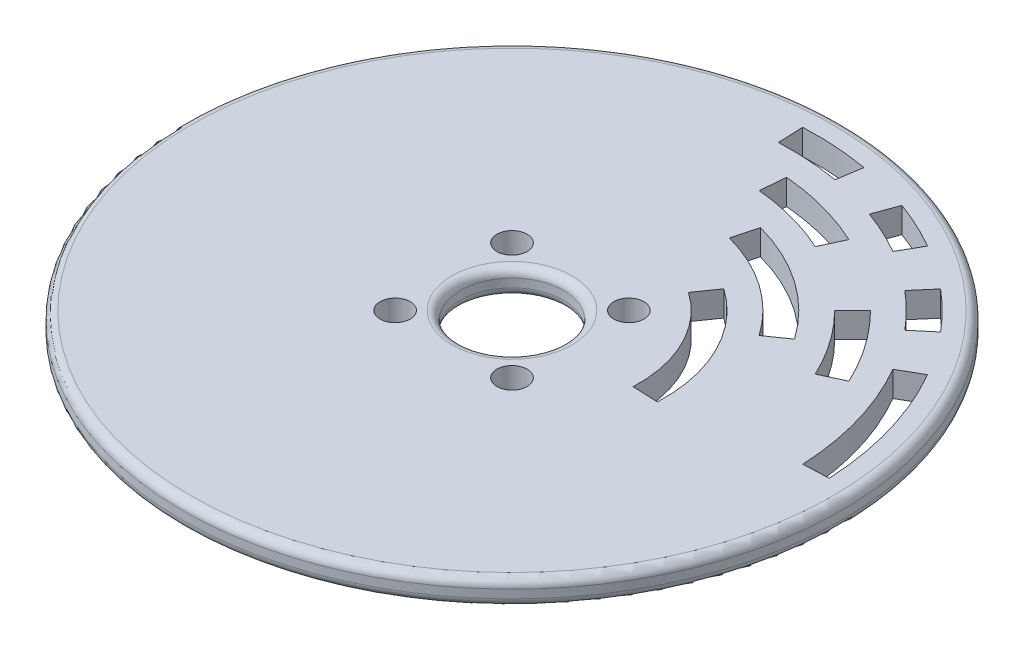
SolidWorks part; units mm, degrees
ref_plane "Front Plane" through (0, 0, 0) normal (0, 0, 1) x (1, 0, 0)
ref_plane "Top Plane" through (0, 0, 0) normal (0, 1, 0) x (1, 0, 0)
ref_plane "Right Plane" through (0, 0, 0) normal (1, 0, 0) x (0, 0, -1)
sketch "Sketch1" plane through (0, 0, 0) normal (0, 1, 0) x (1, 0, 0)
  line L0 (0, 0) -> (8.1776, 8.1776) construction
  circle A0 centre (0, 0) radius 6.096
  circle A1 centre (6.9148, 6.9148) radius 1.7859
  circle A2 centre (6.9148, -6.9148) radius 1.7859
  circle A3 centre (-6.9148, -6.9148) radius 1.7859
  circle A4 centre (-6.9148, 6.9148) radius 1.7859
  point P18 (0, 0)
  dimension "D2" = 3.5719
  dimension "D3" = 4
sketch "Sketch3" plane through (0, 0, 0) normal (0, 1, 0) x (1, 0, 0)
  line L1 (-1.4394, 32.9686) -> (-1.5703, 35.9657) construction
  line L8 (8.6036, 12.2873) -> (10.3244, 14.7447) construction
  line L15 (32.9686, 1.4394) -> (35.9657, 1.5703)
  line L17 (-1.5703, 35.9657) -> (-1.4394, 32.9686)
  line L18 (6.1868, 35.4644) -> (5.7304, 32.4987)
  line L19 (12.3127, 33.8289) -> (11.2867, 31.0099)
  line L20 (18, 31.1769) -> (16.5, 28.5788)
  line L23 (14.9857, -0.6543) -> (17.9829, -0.7851) construction
  line L24 (23.1635, 27.5582) -> (21.212, 25.2795)
  line L25 (27.5776, 23.1404) -> (25.2795, 21.212)
  line L26 (31.1769, 18) -> (28.5788, 16.5)
  line L28 (14.9857, -0.6543) -> (17.9829, -0.7851)
  line L29 (11.2867, 31.0099) -> (12.3127, 33.8289) construction
  line L30 (10.3244, 14.7447) -> (8.6036, 12.2873)
  line L32 (16.5, 28.5788) -> (18, 31.1769) construction
  line L34 (23.3345, 23.3345) -> (25.4558, 25.4558) construction
  line L35 (25.2795, 21.212) -> (27.5776, 23.1404) construction
  line L36 (28.5788, 16.5) -> (31.1769, 18) construction
  line L37 (32.9686, 1.4394) -> (35.9657, 1.5703) construction
  line L38 (2.6147, 29.8858) -> (2.3532, 26.8973)
  line L39 (12.6785, 27.1892) -> (11.4107, 24.4703)
  line L40 (21.2132, 21.2132) -> (19.0919, 19.0919)
  line L41 (27.1892, 12.6785) -> (24.4703, 11.4107)
  line L42 (24.4703, 11.4107) -> (27.1892, 12.6785) construction
  line L43 (2.3532, 26.8973) -> (2.6147, 29.8858) construction
  line L44 (6.2117, 23.1822) -> (5.4352, 20.2844)
  line L45 (19.6596, 13.7658) -> (17.2022, 12.0451)
  line L46 (19.0919, 19.0919) -> (21.2132, 21.2132) construction
  line L47 (17.2022, 12.0451) -> (19.6596, 13.7658) construction
  line L48 (5.4352, 20.2844) -> (6.2117, 23.1822) construction
  line L49 (11.4107, 24.4703) -> (12.6785, 27.1892) construction
  arc A0 (14.9857, -0.6543) -> (8.6036, 12.2873) centre (0, 0) ccw
  arc A1 (17.9829, -0.7851) -> (10.3244, 14.7447) centre (0, 0) ccw
  arc A4 (24.4703, 11.4107) -> (19.0919, 19.0919) centre (0, 0) ccw
  arc A5 (27.1892, 12.6785) -> (21.2132, 21.2132) centre (0, 0) ccw
  arc A6 (32.9686, 1.4394) -> (28.5788, 16.5) centre (0, 0) ccw
  arc A7 (35.9657, 1.5703) -> (31.1769, 18) centre (0, 0) ccw
  arc A8 (25.2795, 21.212) -> (21.212, 25.2795) centre (0, 0) ccw
  arc A9 (27.5776, 23.1404) -> (23.1635, 27.5582) centre (0, 0) ccw
  arc A10 (18, 31.1769) -> (12.3127, 33.8289) centre (0, 0) ccw
  arc A11 (16.5, 28.5788) -> (11.2867, 31.0099) centre (0, 0) ccw
  arc A12 (6.1868, 35.4644) -> (-1.5703, 35.9657) centre (0, 0) ccw
  arc A13 (5.7304, 32.4987) -> (-1.4394, 32.9686) centre (0, 0) ccw
  arc A14 (17.2022, 12.0451) -> (5.4352, 20.2844) centre (0, 0) ccw
  arc A15 (19.6596, 13.7658) -> (6.2117, 23.1822) centre (0, 0) ccw
  arc A16 (11.4107, 24.4703) -> (2.3532, 26.8973) centre (0, 0) ccw
  arc A17 (12.6785, 27.1892) -> (2.6147, 29.8858) centre (0, 0) ccw
  point P14 (0, 0)
  point P16 (0, 0)
  point P19 (0, 0)
  point P27 (0, 0)
  point P29 (0, 0)
  point P32 (0, 0)
  point P33 (0, 0)
  point P51 (0, 0)
  point P57 (0, 0)
sketch "Sketch4" plane through (0, 0, 0) normal (0, 1, 0) x (1, 0, 0)
  circle A0 centre (0, 0) radius 39
extrude "Boss-Extrude1" add sketch "Sketch4" along normal blind 3
extrude "Cut-Extrude1" cut sketch "Sketch3" along normal blind 3
extrude "Cut-Extrude3" cut sketch "Sketch1" along normal blind 3
fillet "Fillet1" radius 1 4 edges at (0, 0, 6.096) (0, 3, 6.096) (0, 3, 39) (0, 0, 39)
